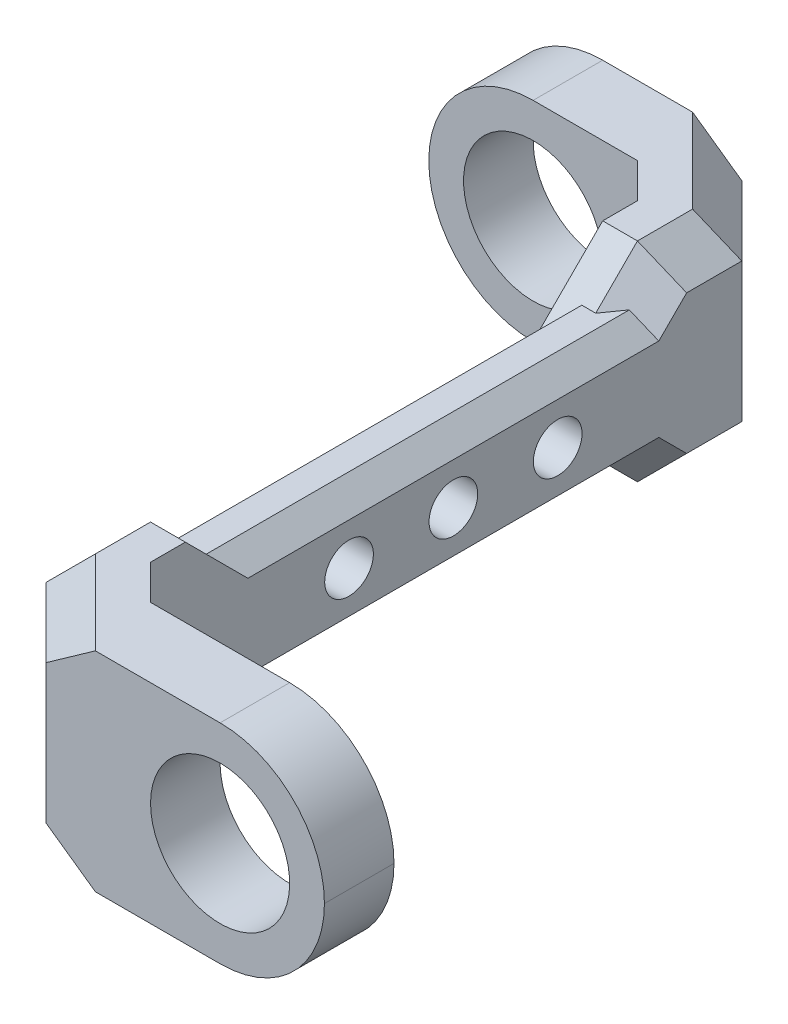
SolidWorks part; units mm, degrees
ref_plane "前视基准面" through (0, 0, 0) normal (0, 0, 1) x (1, 0, 0)
ref_plane "上视基准面" through (0, 0, 0) normal (0, 1, 0) x (1, 0, 0)
ref_plane "右视基准面" through (0, 0, 0) normal (1, 0, 0) x (0, 0, -1)
other "Configuration Table"
sketch "Sketch1" plane through (0, 0, 0) normal (0, 0, 1) x (1, 0, 0)
  line L0 (0, 7.5) -> (15, 7.5)
  line L1 (0, -7.5) -> (15, -7.5)
  line L2 (15, -7.5) -> (15, 7.5)
  circle A0 centre (0, 0) radius 7.5
  circle A1 centre (0, 0) radius 5
  dimension "D1" = 15
  dimension "D2" = 10
  dimension "D3" = 15
extrude "Boss-Extrude1" add sketch "Sketch1" along normal blind 5 contours A0 A1 | A0 L1 L2 L0
sketch "Sketch2" plane through (0, 0, 5) normal (0, 0, 1) x (1, 0, 0)
  line L0 (0, -7.5) -> (15, -7.5) construction
  line L1 (15, 7.5) -> (10, 7.5)
  line L2 (15, 7.5) -> (15, -7.5)
  line L3 (15, -7.5) -> (10, -7.5)
  line L4 (10, 7.5) -> (10, -7.5)
  dimension "D1" = 5
extrude "Boss-Extrude2" add sketch "Sketch2" along normal blind 50
sketch "Sketch3" plane through (15, 0, 0) normal (1, 0, 0) x (0, 0, -1)
  line L5 (-55, -7.5) -> (0, -7.5) construction
  line L6 (-55, 7.5) -> (-50, 7.5)
  line L7 (-55, 7.5) -> (-55, -7.5)
  line L8 (-55, -7.5) -> (-50, -7.5)
  line L9 (-50, 7.5) -> (-50, -7.5)
  dimension "D1" = 5
extrude "Boss-Extrude3" add sketch "Sketch3" along normal blind 20
sketch "Sketch4" plane through (0, 0, 50) normal (0, 0, -1) x (-1, 0, 0)
  line L0 (-35, 0) -> (-27.5, 0) construction
  line L1 (-35, -7.5) -> (-35, 7.5) construction
  circle A0 centre (-27.5, 0) radius 5
  dimension "D1" = 10
  dimension "D2" = 7.5
extrude "Cut-Extrude1" cut sketch "Sketch4" against normal blind 15
fillet "Fillet1" radius 7.5 2 edges at (35, -7.5, 52.5) (35, 7.5, 52.5)
chamfer "Chamfer1" distance 5 angle 45 2 edges at (15, 0, 0) (10, 0, 55)
sketch "Sketch5" plane through (10, 0, 0) normal (-1, 0, 0) x (0, 0, 1)
  line L0 (10, -7.5) -> (13, -4.5)
  line L1 (13, -4.5) -> (42, -4.5)
  line L2 (42, -4.5) -> (45, -7.5)
  line L3 (50, -7.5) -> (5, -7.5) construction
  line L4 (45, -7.5) -> (10, -7.5)
  line L5 (10, 0) -> (50, 0) construction
  line L7 (50, -7.5) -> (50, 7.5) construction
  line L8 (45, 7.5) -> (10, 7.5)
  line L9 (42, 4.5) -> (45, 7.5)
  line L10 (13, 4.5) -> (42, 4.5)
  line L11 (10, 7.5) -> (13, 4.5)
  line L12 (10, -7.5) -> (10, 7.5) construction
  line L13 (10, 0) -> (5, 0) construction
  line L14 (5, 7.5) -> (5, -7.5) construction
  line L15 (45, 7.5) -> (45, -7.8614) construction
  dimension "D1" = 35
  dimension "D2" = 45
  dimension "D3" = 45
  dimension "D4" = 3
  dimension "D5" = 5
extrude "Cut-Extrude2" cut sketch "Sketch5" against normal blind 5
chamfer "Chamfer2" distance 1.5 angle 45 4 edges at (15, -4.5, 27.5) (15, 4.5, 27.5) (10, 4.5, 27.5) (10, -4.5, 27.5)
chamfer "Chamfer3" distance 2.5 angle 45 16 edges at (10.75, 3.75, 41.25) (10.75, -3.75, 41.25) (14.25, -3.75, 13.75) (14.25, 3.75, 13.75) (10, 7.5, 47.5) (12.5, 7.5, 52.5) (12.5, 7.5, 2.5) (10, -7.5, 47.5) (12.5, -7.5, 52.5) (12.5, -7.5, 2.5) (15, 7.5, 7.5) (15, -7.5, 7.5) (15, -5.25, 12.25) (10, -5.25, 42.75) (15, 5.25, 12.25) (10, 5.25, 42.75)
chamfer "Chamfer4" distance 2.5 angle 45 2 edges at (15, 0, 50) (10, 0, 5)
sketch "Sketch10" plane through (15, 0, 0) normal (1, 0, 0) x (0, 0, -1)
  line L0 (-25.7322, 3) -> (-25.7322, -3) construction
  line L1 (-10.9645, 3) -> (-40.5, 3) construction
  line L2 (-40.5, -3) -> (-10.9645, -3) construction
  line L3 (-25.7322, -3) -> (-25.7322, 0) construction
  line L4 (-25.7322, 0) -> (-18.2322, 0) construction
  circle A0 centre (-25.7322, 0) radius 1.75
  circle A1 centre (-18.2322, 0) radius 1.75
  circle A2 centre (-33.2322, 0) radius 1.75
  dimension "D1" = 3.5
  dimension "D3" = 3.5
  dimension "D2" = 7.5
extrude "Cut-Extrude4" cut sketch "Sketch10" against normal blind 10
